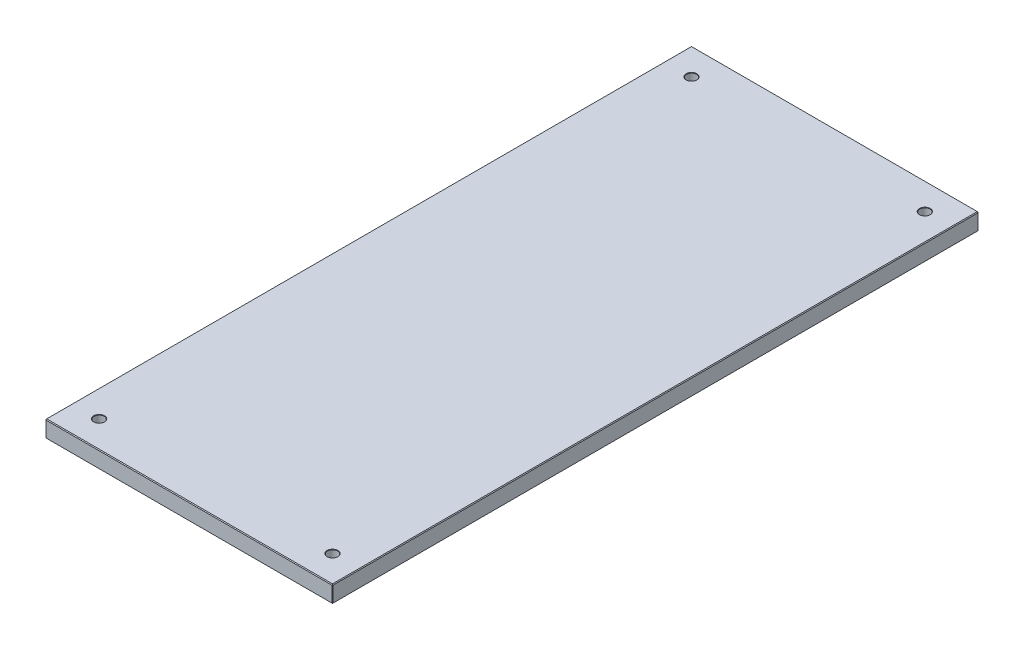
SolidWorks part; units mm, degrees
material "Pine"
ref_plane "Front Plane" through (0, 0, 0) normal (0, 0, 1) x (1, 0, 0)
ref_plane "Top Plane" through (0, 0, 0) normal (0, 1, 0) x (1, 0, 0)
ref_plane "Right Plane" through (0, 0, 0) normal (1, 0, 0) x (0, 0, -1)
ref_axis "X Axis" through (111.76, 0, 0) along (-1, 0, 0)
ref_axis "Y Axis" through (0, 3.4925, 0) along (0, -1, 0)
ref_axis "Z Axis" through (0, 0, -167.64) along (0, 0, 1)
sketch "Sketch1" plane through (0, 0, 0) normal (0, 1, 0) x (1, 0, 0)
  line L1 (-101.6, -228.6) -> (101.6, -228.6)
  line L2 (-101.6, -228.6) -> (-101.6, 228.6)
  line L3 (-101.6, 228.6) -> (101.6, 228.6)
  line L4 (101.6, -228.6) -> (101.6, 228.6)
  line L5 (0, 228.6) -> (0, -228.6) construction
  line L6 (-101.6, 0) -> (101.6, 0) construction
  point P0 (0, 0)
  dimension "D1" = 457.2
  dimension "D2" = 203.2
extrude "Boss-Extrude1" add sketch "Sketch1" along normal mid plane 12
sketch "Sketch2" plane through (0, 0, 0) normal (0, 1, 0) x (1, 0, 0)
  line L14 (-82.55, -209.55) -> (82.55, -209.55)
  line L15 (82.55, -209.55) -> (82.55, 209.55)
  line L16 (-82.55, 209.55) -> (-82.55, -209.55)
  line L17 (82.55, 209.55) -> (-82.55, 209.55)
  line L18 (-82.55, -209.55) -> (82.55, -209.55) construction
  line L19 (82.55, -209.55) -> (82.55, 209.55) construction
  line L20 (-82.55, 209.55) -> (-82.55, -209.55) construction
  line L21 (82.55, 209.55) -> (-82.55, 209.55) construction
  dimension "D1" = 19.05
sketch "Sketch6" plane through (0, 6, 0) normal (0, 1, 0) x (1, 0, 0)
  point P0 (-82.55, 209.55)
  point P3 (82.55, 209.55)
  point P6 (82.55, -209.55)
  point P9 (-82.55, -209.55)
hole_wizard "1/4 Clearance Hole1" positions "Sketch6" profile "Sketch4" hole size "1/4" standard "ANSI Inch" end condition through all
sketch "Sketch4" plane through (-82.55, 6, -209.55) normal (1, 0, 0) x (0, 0, 1)
  line L0 (0, 0) -> (0, 12)
  line L1 (0, 12) -> (3.8252, 12)
  line L2 (3.5712, 11.746) -> (3.5712, 0.254)
  line L3 (3.5712, 0.254) -> (3.8252, 0)
  line L5 (3.8252, 0) -> (0, 0)
  line L6 (-3.5712, 0.254) -> (-3.8252, 0) construction
  line L7 (3.8252, 12) -> (3.5712, 11.746)
  line L8 (-3.8252, 12) -> (-3.5712, 11.746) construction
  line L11 (0, -6.35) -> (0, 107.95) construction
  dimension "Thru Hole Dia." = 7.1425
  dimension "Thru Hole Depth" = 12
  dimension "Near C'Sink Dia." = 7.6505
  dimension "Near C'Sink Angle" = 90
  dimension "Far C'Sink Dia." = 7.6505
  dimension "Far C'Sink Angle" = 90
chamfer "Chamfer1" distance 0.508 angle 45 12 edges at (101.6, 6, 0) (101.6, -6, 0) (101.6, 0, -228.6) (0, 6, -228.6) (0, -6, -228.6) (-101.6, 0, -228.6) (-101.6, 6, 0) (-101.6, -6, 0) (-101.6, 0, 228.6) (0, 6, 228.6) (101.6, 0, 228.6) (0, -6, 228.6)
move or copy body "Body-Move/Copy1" [suppressed] bodies to move or copy 102 parameters "D1"=0, "D2"=0, "D3"=0
move or copy body "Body-Move/Copy2" [suppressed] bodies to move or copy 103 parameters "D1"=0, "D2"=0, "D3"=0
